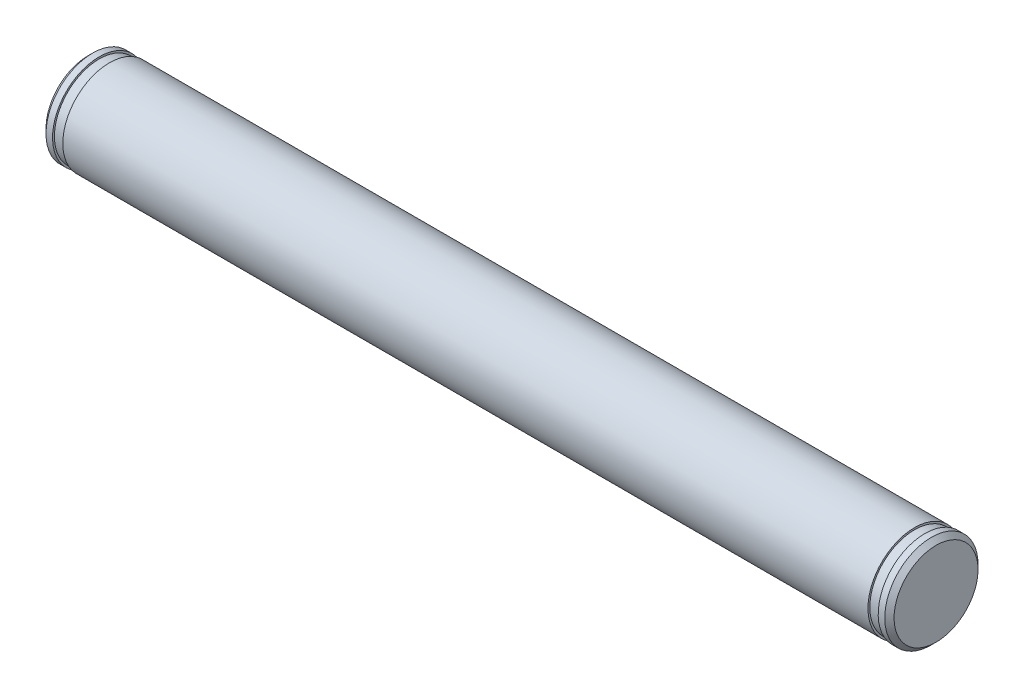
SolidWorks part; units mm, degrees
ref_plane "前视基准面" through (0, 0, 0) normal (0, 0, 1) x (1, 0, 0)
ref_plane "上视基准面" through (0, 0, 0) normal (0, 1, 0) x (1, 0, 0)
ref_plane "右视基准面" through (0, 0, 0) normal (1, 0, 0) x (0, 0, -1)
other "Configuration Table"
sketch "草图1" plane through (0, 0, 0) normal (0, 0, 1) x (1, 0, 0)
  line L0 (-45.45, 0) -> (45.45, 0) construction
  line L1 (45.45, 0) -> (45.45, 5)
  line L2 (45.45, 5) -> (44.25, 5)
  line L3 (44.25, 5) -> (44.25, 4.8)
  line L4 (44.25, 4.8) -> (43.15, 4.8)
  line L5 (43.15, 4.8) -> (43.15, 5)
  line L6 (43.15, 5) -> (-43.15, 5)
  line L7 (0, 5) -> (0, 0) construction
  line L8 (43.25, 4.8) -> (43.25, 0) construction
  line L9 (-45.45, 0) -> (-45.45, 5)
  line L10 (-43.25, 4.8) -> (-43.25, 0) construction
  line L11 (-43.15, 4.8) -> (-43.15, 5)
  line L12 (-44.25, 4.8) -> (-43.15, 4.8)
  line L13 (-44.25, 5) -> (-44.25, 4.8)
  line L14 (-45.45, 5) -> (-44.25, 5)
  line L15 (45.45, 0) -> (-45.45, 0)
  dimension "D1" = 1.1
  dimension "D2" = 1
  dimension "D3" = 10
  dimension "D4" = 9.6
  dimension "D5" = 1.2
  dimension "D6" = 86.5
revolve "旋转1" add sketch "草图1" angle 360 about L15
chamfer "倒角1" distance 0.5 angle 45 2 edges at (45.45, 5, 0) (-45.45, 5, 0)
ref_plane "基准面1" through (43.25, 0, 0) normal (1, 0, 0) x (0, 0, -1)
ref_axis "基准轴1" through (-43.15, 0, 0) along (1, 0, 0)
